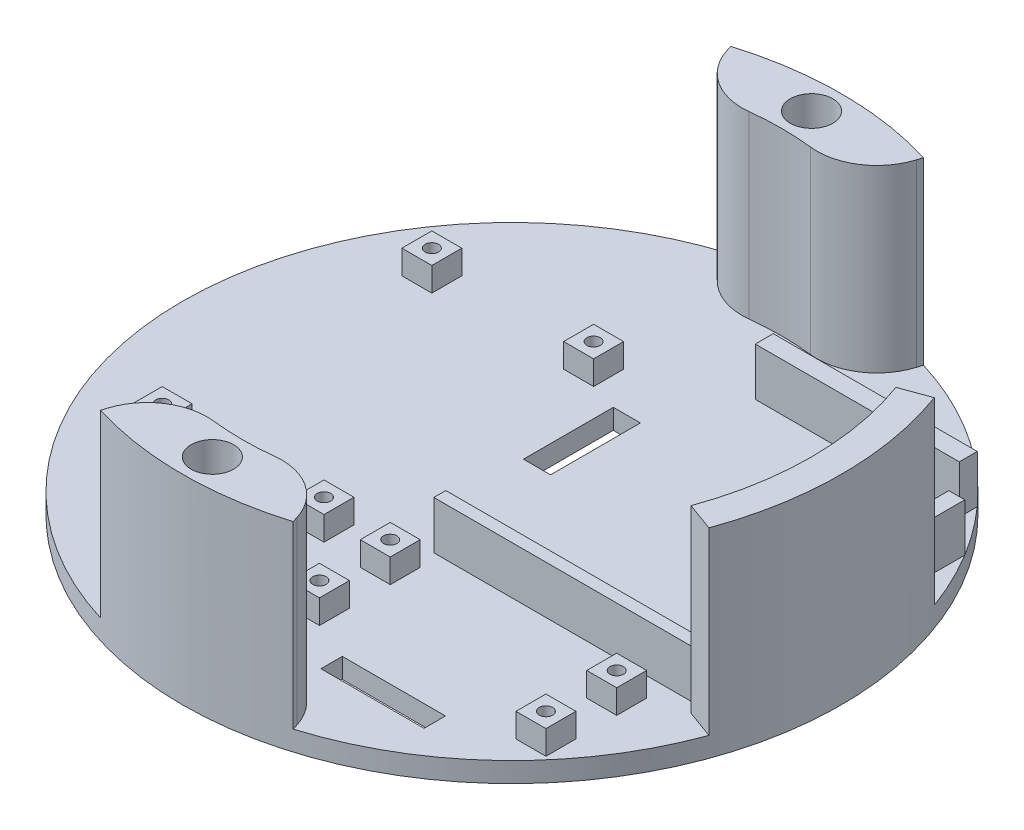
SolidWorks part; units mm, degrees
ref_plane "Front Plane" through (0, 0, 0) normal (0, 0, 1) x (1, 0, 0)
ref_plane "Top Plane" through (0, 0, 0) normal (0, 1, 0) x (1, 0, 0)
ref_plane "Right Plane" through (0, 0, 0) normal (1, 0, 0) x (0, 0, -1)
sketch "Sketch2" plane through (0, 0, 0) normal (0, 1, 0) x (1, 0, 0)
  circle A0 centre (0, 0) radius 69.85
  dimension "D1" = 139.7
extrude "Boss-Extrude1" add sketch "Sketch2" along normal blind 4.2333
sketch "Sketch3" plane through (0, 4.2333, 0) normal (0, 1, 0) x (1, 0, 0)
  line L0 (-20.4222, 66.7979) -> (-16.709, 54.6528)
  line L5 (20.4222, 66.7979) -> (16.709, 54.6528)
  line L6 (16.709, -54.6528) -> (20.4222, -66.7979)
  line L7 (-16.709, -54.6528) -> (-20.4222, -66.7979)
  arc A6 (20.4222, 66.7979) -> (-20.4222, 66.7979) centre (0, 0) ccw
  arc A7 (-16.709, -54.6528) -> (16.709, -54.6528) centre (0, 0) ccw
  arc A8 (-20.4222, -66.7979) -> (20.4222, -66.7979) centre (0, 0) ccw
  arc A9 (16.709, 54.6528) -> (-16.709, 54.6528) centre (0, 0) ccw
  circle M3 centre (0, 0) radius 69.85
  dimension "D1" = 114.3
extrude "Boss-Extrude2" add sketch "Sketch3" along normal blind 38.1 contours A7 L7 L6 M3 | A9 L5 L0 M3
fillet "Fillet3" radius 12.7 1 edges at (-16.709, 23.2833, -54.6528) type face fillet first side face at (-18.5656, 23.2833, -60.7254) second side face at (0, 23.2833, -55.9014)
fillet "Fillet4" radius 12.7 1 edges at (16.709, 23.2833, 54.6528) type face fillet first side face at (0, 23.2833, 55.9014) second side face at (18.5656, 23.2833, 60.7254)
fillet "Fillet5" radius 12.7 1 edges at (-16.709, 23.2833, 54.6528) type face fillet first side face at (-5.1625, 23.2833, 56.3139) second side face at (-18.5656, 23.2833, 60.7254)
sketch "Sketch4" plane through (0, 4.2333, 0) normal (0, 1, 0) x (1, 0, 0)
  line L0 (59.6705, 21.7183) -> (65.6375, 23.8901)
  line L1 (59.6705, -21.7183) -> (65.6375, -23.8901)
  arc A0 (65.6375, -23.8901) -> (65.6375, 23.8901) centre (0, 0) ccw
  arc A1 (59.6705, -21.7183) -> (59.6705, 21.7183) centre (0, 0) ccw
  dimension "D1" = 127
extrude "Boss-Extrude3" add sketch "Sketch4" along normal blind 38.1
sketch "Sketch5" plane through (0, 42.3333, 0) normal (0, 1, 0) x (1, 0, 0)
  circle A0 centre (0, 63.5) radius 4.5085
  circle A1 centre (0, -63.5) radius 4.5085
  arc A3 (-20.4222, -66.7979) -> (20.4222, -66.7979) centre (0, 0) ccw construction
  point P7 (0, -69.85)
  dimension "D1" = 9.017
  dimension "D2" = 9.017
  dimension "D3" = 127
  dimension "D4" = 6.35
extrude "Cut-Extrude1" cut sketch "Sketch5" against normal through all both and the other way through all
fillet "Fillet6" radius 12.7 1 edges at (16.709, 23.2833, -54.6528) type face fillet first side face at (5.1625, 23.2833, -56.3139) second side face at (18.5656, 23.2833, -60.7254)
sketch "Sketch6" plane through (0, 4.2333, 0) normal (0, 1, 0) x (1, 0, 0)
  line L0 (-16.972, 27.9284) -> (-16.972, 34.2784)
  line L1 (-51.262, 27.9284) -> (-44.912, 27.9284)
  line L2 (-51.262, 27.9284) -> (-51.262, 34.2784)
  line L3 (-51.262, 34.2784) -> (-44.912, 34.2784)
  line L4 (-44.912, 27.9284) -> (-44.912, 34.2784)
  line L5 (-51.262, 27.9284) -> (-44.912, 34.2784) construction
  line L6 (-51.262, 34.2784) -> (-44.912, 27.9284) construction
  line L7 (-16.972, 27.9284) -> (-10.622, 27.9284)
  line L8 (-10.622, 27.9284) -> (-10.622, 34.2784)
  line L9 (-16.972, 34.2784) -> (-10.622, 34.2784)
  line L10 (-16.972, -29.2216) -> (-16.972, -22.8716)
  line L11 (-16.972, -29.2216) -> (-10.622, -29.2216)
  line L12 (-10.622, -29.2216) -> (-10.622, -22.8716)
  line L13 (-16.972, -22.8716) -> (-10.622, -22.8716)
  line L14 (-51.262, -29.2216) -> (-51.262, -22.8716)
  line L15 (-51.262, -29.2216) -> (-44.912, -29.2216)
  line L16 (-44.912, -29.2216) -> (-44.912, -22.8716)
  line L17 (-51.262, -22.8716) -> (-44.912, -22.8716)
  line L18 (52.1951, -23.6442) -> (52.1951, -29.9942)
  line L23 (52.1951, -23.6442) -> (45.8451, -23.6442)
  line L24 (45.8451, -23.6442) -> (45.8451, -29.9942)
  line L25 (52.1951, -29.9942) -> (45.8451, -29.9942)
  line L26 (4.1942, -23.6442) -> (4.1942, -29.9942)
  line L27 (4.1942, -23.6442) -> (-2.1558, -23.6442)
  line L28 (-2.1558, -23.6442) -> (-2.1558, -29.9942)
  line L29 (4.1942, -29.9942) -> (-2.1558, -29.9942)
  line L30 (4.1942, -38.6455) -> (4.1942, -44.9955)
  line L31 (4.1942, -38.6455) -> (-2.1558, -38.6455)
  line L32 (-2.1558, -38.6455) -> (-2.1558, -44.9955)
  line L33 (4.1942, -44.9955) -> (-2.1558, -44.9955)
  line L34 (52.1951, -38.6455) -> (52.1951, -44.9955)
  line L35 (52.1951, -38.6455) -> (45.8451, -38.6455)
  line L36 (45.8451, -38.6455) -> (45.8451, -44.9955)
  line L37 (52.1951, -44.9955) -> (45.8451, -44.9955)
  line L38 (52.1951, -23.6442) -> (4.1942, -23.6442) construction
  line L40 (8.8729, 42.706) -> (52.1084, 42.706)
  line L43 (56.2961, 36.3106) -> (56.2961, -16.984)
  line L44 (8.8729, 46.516) -> (52.1084, 46.516)
  line L45 (56.2961, -19.524) -> (60.424, -19.524)
  line L46 (59.6705, 21.7183) -> (59.6705, 36.3106)
  line L47 (59.6705, 36.3106) -> (56.2961, 36.3106)
  line L48 (52.1084, 46.516) -> (52.1084, 42.706)
  line L49 (8.8729, 46.516) -> (8.8729, 42.706)
  line L50 (2.9561, -16.984) -> (56.2961, -16.984)
  line L51 (2.9561, -16.984) -> (2.9561, -19.524)
  line L52 (2.9561, -19.524) -> (56.2961, -19.524)
  circle A0 centre (-48.087, 31.1034) radius 1.425
  circle A1 centre (-13.797, 31.1034) radius 1.425
  circle A2 centre (-13.797, -26.0466) radius 1.425
  circle A3 centre (-48.087, -26.0466) radius 1.425
  circle A4 centre (49.0201, -26.8192) radius 1.425
  circle A5 centre (1.0192, -26.8192) radius 1.425
  circle A6 centre (1.0192, -41.8205) radius 1.425
  circle A7 centre (49.0201, -41.8205) radius 1.425
  arc A8 (65.6375, 23.8901) -> (20.4222, 66.7979) centre (0, 0) ccw construction
  arc A10 (59.6705, -21.7183) -> (59.6705, 21.7183) centre (0, 0) ccw construction
  arc A11 (59.6705, 21.7183) -> (60.424, -19.524) centre (0, 0) cw
  point P6 (59.6705, 36.3106)
  arc M62 (59.6705, -21.7183) -> (59.6705, 21.7183) centre (0, 0) ccw
  dimension "D1" = 2.85
  dimension "D2" = 6.35
  dimension "D3" = 2
  dimension "D5" = 2.54
  dimension "D6" = 38.7023
  dimension "D11" = 48.0009
  dimension "D12" = 34.29
  dimension "D13" = 57.15
  dimension "D4" = 2
  dimension "D9" = 2
  dimension "D10" = 2
extrude "Boss-Extrude4" add sketch "Sketch6" along normal blind 10.16 contours L51 L52 L45 L46 L47 L43 L50 M62 | L44 L49 L40 L48 region at (30.4907, 4.2333, -44.611) region at (57.9833, 4.2333, -35.487)
extrude "Boss-Extrude5" add sketch "Sketch6<3>" along normal blind 5.08 contours L1 L4 L3 L2 A0 | L9 L0 L7 L8 A1 | L13 L10 L11 L12 A2 | L29 L26 L27 L28 A5 | L17 L14 L15 L16 A3 | L33 L30 L31 L32 A6 | L37 L34 L35 L36 A7 | L25 L18 L23 L24 A4 region at (-16.8822, 4.2333, -31.1034) region at (-51.1722, 4.2333, -31.1034) region at (-16.8822, 4.2333, 26.0466) region at (-51.1722, 4.2333, 26.0466) region at (52.1053, 4.2333, 26.8192) region at (4.1044, 4.2333, 26.8192) region at (4.1044, 4.2333, 41.8205) region at (52.1053, 4.2333, 41.8205)
sketch "Sketch6<3>" plane through (0, 4.2333, 0) normal (0, 1, 0) x (1, 0, 0) same geometry as "Sketch6"
sketch "Sketch7" plane through (0, 9.3133, 0) normal (0, 1, 0) x (1, 0, 0)
  line L1 (12.2766, -48.2411) -> (34.1461, -48.2411)
  line L2 (12.2766, -48.2411) -> (12.2766, -52.7737)
  line L3 (12.2766, -52.7737) -> (34.1461, -52.7737)
  line L4 (34.1461, -48.2411) -> (34.1461, -52.7737)
  line L5 (-4.7205, 26.2061) -> (1.0192, 26.2061)
  line L6 (-4.7205, 26.2061) -> (-4.7205, 7.1561)
  line L7 (-4.7205, 7.1561) -> (1.0192, 7.1561)
  line L8 (1.0192, 26.2061) -> (1.0192, 7.1561)
  circle A0 centre (-48.087, 31.1034) radius 1.425
  circle A1 centre (-13.797, 31.1034) radius 1.425
  circle A2 centre (1.0192, -41.8205) radius 1.425
  circle A3 centre (1.0192, -26.8192) radius 1.425
  circle A4 centre (-13.797, -26.0466) radius 1.425
  circle A5 centre (-48.087, -26.0466) radius 1.425
  circle A6 centre (49.0201, -26.8192) radius 1.425
  circle A7 centre (49.0201, -41.8205) radius 1.425
  dimension "D1" = 19.05
  dimension "D2" = 5.7398
extrude "Cut-Extrude2" cut sketch "Sketch7" against normal through all both and the other way through all
